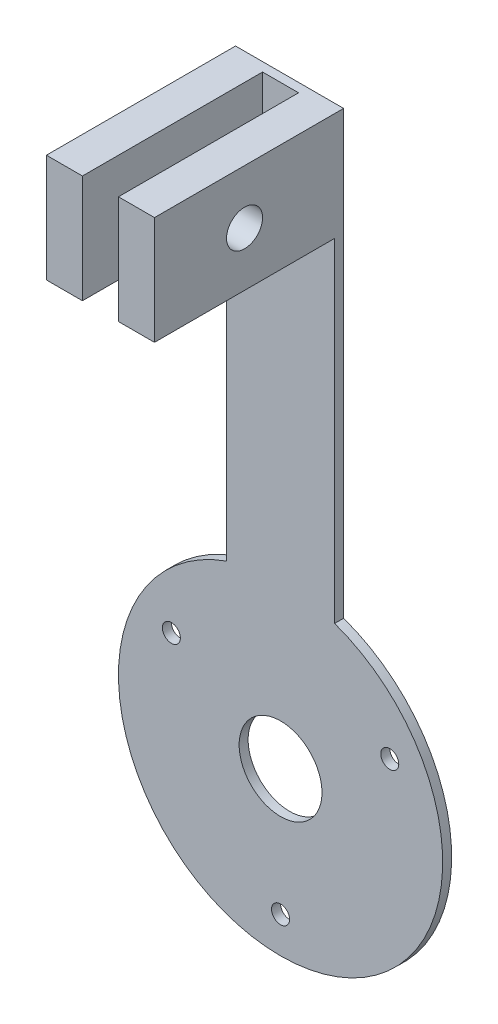
SolidWorks part; units mm, degrees
ref_plane "Front Plane" through (0, 0, 0) normal (0, 0, 1) x (1, 0, 0)
ref_plane "Top Plane" through (0, 0, 0) normal (0, 1, 0) x (1, 0, 0)
ref_plane "Right Plane" through (0, 0, 0) normal (1, 0, 0) x (0, 0, -1)
sketch "Sketch1" plane through (0, 0, 0) normal (0, 0, 1) x (1, 0, 0)
  line L1 (-88.9, 88.9) -> (88.9, 88.9)
  line L2 (-88.9, 88.9) -> (-88.9, -88.9)
  line L3 (-88.9, -88.9) -> (88.9, -88.9)
  line L4 (88.9, 88.9) -> (88.9, -88.9)
  line L5 (-88.9, 88.9) -> (88.9, -88.9) construction
  line L6 (-88.9, -88.9) -> (88.9, 88.9) construction
  line L7 (-19.05, 88.9) -> (19.05, 88.9)
  line L8 (-19.05, 88.9) -> (-19.05, 209.55)
  line L9 (-19.05, 209.55) -> (19.05, 209.55)
  line L10 (19.05, 88.9) -> (19.05, 209.55)
  circle A0 centre (0, 0) radius 14.605
  point P0 (0, 0)
  point P12 (0, 0)
  point P13 (0, 0)
  point P14 (0, 88.9)
  dimension "D2" = 29.21
  dimension "D1" = 177.8
  dimension "D3" = 38.1
  dimension "D4" = 120.65
extrude "Boss-Extrude1" add sketch "Sketch1" along normal blind 3.175 contours L1 L10 L9 L8 | L4 L1 L2 L3 A0 region at (-53.975, 86.3855, 0) region at (0, 149.225, 0)
sketch "Sketch2" plane through (0, 0, 3.175) normal (0, 0, 1) x (1, 0, 0)
  line L0 (-19.05, 209.55) -> (19.05, 209.55) construction
  line L1 (1.8142, 0) -> (50001.8142, 0) construction
  line L2 (0, 88.9) -> (0, 0) construction
  line L3 (0, 88.9) -> (-76.9897, -44.45) construction
  line L4 (-76.9897, -44.45) -> (76.9897, -44.45) construction
  line L5 (76.9897, -44.45) -> (0, 88.9) construction
  line L6 (-76.9897, -44.45) -> (0, 0) construction
  line L7 (0, 0) -> (76.9897, 44.45) construction
  line L8 (76.9897, -44.45) -> (0, 0) construction
  line L9 (0, 0) -> (-76.9897, 44.45) construction
  line L10 (0, 0) -> (0, -88.9) construction
  line L19 (88.9, -88.9) -> (88.9, 88.9)
  line L20 (88.9, 88.9) -> (-88.9, 88.9)
  line L21 (-88.9, 88.9) -> (-88.9, -88.9)
  line L22 (-88.9, -88.9) -> (88.9, -88.9)
  line L27 (-6.35, 209.55) -> (6.35, 209.55) construction
  line L28 (-19.05, 209.55) -> (-6.35, 209.55)
  line L29 (-19.05, 209.55) -> (-19.05, 171.45)
  line L30 (-19.05, 171.45) -> (-6.35, 171.45)
  line L31 (-6.35, 209.55) -> (-6.35, 171.45)
  line L32 (6.35, 209.55) -> (19.05, 209.55)
  line L33 (6.35, 209.55) -> (6.35, 171.45)
  line L34 (6.35, 171.45) -> (19.05, 171.45)
  line L35 (19.05, 209.55) -> (19.05, 171.45)
  circle A0 centre (0, 0) radius 88.9
  circle A1 centre (-38.4948, 22.225) radius 3.175
  circle A2 centre (0, -44.45) radius 3.175
  circle A3 centre (38.4948, 22.225) radius 3.175
  point P4 (0, 0)
  point P5 (-128.8861, -109.911)
  point P21 (-69.85, 88.9)
  point P23 (-69.85, -88.9)
  point P25 (69.85, -88.9)
  point P26 (69.85, 88.9)
  point P27 (-57.15, 88.9)
  point P28 (-57.15, -88.9)
  point P29 (57.15, -88.9)
  point P30 (57.15, 88.9)
  point P39 (0, 0)
  point P40 (0, 0)
  point P41 (12.8511, 77.6746)
  point P42 (31.75, 46.9484)
  point P43 (0, 209.55)
  point P44 (0, 0)
  point P45 (19.05, 77.9274)
  point P46 (31.75, 88.9)
  point P47 (19.05, 144.58)
  point P48 (6.35, 215.9)
  point P51 (38.4948, 22.225)
  dimension "D1" = 6.35
  dimension "D2" = 177.8
  dimension "D5" = 38.1
  dimension "D3" = 12.7
  dimension "D4" = 12.7
  dimension "D6" = 38.1
extrude "Cut-Extrude1" cut sketch "Sketch2" against normal through all contours A1 | A3 | A2 region at (-38.4948, 22.225, 3.175) region at (0, -44.45, 3.175) region at (38.4948, 22.225, 3.175)
extrude "Boss-Extrude2" add sketch "Sketch2<3>" along normal blind 63.5 contours L29 L31 | L35 L32 L33 L34 region at (-12.7, 190.5, 3.175) region at (12.7, 190.5, 3.175)
sketch "Sketch2<3>" plane through (0, 0, 3.175) normal (0, 0, 1) x (1, 0, 0) same geometry as "Sketch2"
sketch "Sketch3" plane through (-19.05, 0, 0) normal (-1, 0, 0) x (0, 0, 1)
  line L0 (66.675, 190.5) -> (34.925, 190.5) construction
  line L4 (66.675, 209.55) -> (66.675, 171.45) construction
  circle A2 centre (34.925, 190.5) radius 6.35
  point P2 (0, 0)
  dimension "D1" = 12.7
  dimension "D2" = 31.75
extrude "Cut-Extrude2" cut sketch "Sketch3" against normal through all contours A2 | A2 region at (-19.05, 190.5, 34.925)
sketch "Sketch4" plane through (0, 0, 3.175) normal (0, 0, 1) x (1, 0, 0)
  line L0 (0, 0) -> (49.4934, 28.575) construction
  line L1 (-19.05, 88.9) -> (-19.05, 53.8815)
  line L2 (19.05, 88.9) -> (19.05, 53.8815)
  line L12 (19.05, 171.45) -> (6.35, 171.45)
  line L13 (6.35, 171.45) -> (6.35, 209.55)
  line L14 (6.35, 209.55) -> (-6.35, 209.55)
  line L15 (-6.35, 209.55) -> (-6.35, 171.45)
  line L16 (-6.35, 171.45) -> (-19.05, 171.45)
  line L17 (-19.05, 171.45) -> (-19.05, 88.9)
  line L18 (-19.05, 88.9) -> (-88.9, 88.9)
  line L19 (-88.9, 88.9) -> (-88.9, -88.9)
  line L20 (-88.9, -88.9) -> (88.9, -88.9)
  line L21 (88.9, -88.9) -> (88.9, 88.9)
  line L22 (88.9, 88.9) -> (19.05, 88.9)
  line L23 (19.05, 88.9) -> (19.05, 171.45)
  line L24 (19.05, 171.45) -> (6.35, 171.45)
  line L25 (6.35, 171.45) -> (6.35, 209.55)
  line L26 (6.35, 209.55) -> (-6.35, 209.55)
  line L27 (-6.35, 209.55) -> (-6.35, 171.45)
  line L28 (-6.35, 171.45) -> (-19.05, 171.45)
  line L29 (-19.05, 171.45) -> (-19.05, 88.9)
  line L30 (-19.05, 88.9) -> (-88.9, 88.9)
  line L31 (-88.9, 88.9) -> (-88.9, -88.9)
  line L32 (-88.9, -88.9) -> (88.9, -88.9)
  line L33 (88.9, -88.9) -> (88.9, 88.9)
  line L34 (88.9, 88.9) -> (19.05, 88.9)
  line L35 (19.05, 88.9) -> (19.05, 171.45)
  circle A0 centre (0, 0) radius 57.15
  point P6 (38.4948, 22.225)
  point P10 (49.4934, 28.575)
  point P12 (27.2419, 28.1124)
  line M26 (-19.05, 88.9) -> (-88.9, 88.9)
  line M27 (-88.9, 88.9) -> (-88.9, -88.9)
  line M28 (-88.9, -88.9) -> (88.9, -88.9)
  line M29 (88.9, -88.9) -> (88.9, 88.9)
  line M30 (88.9, 88.9) -> (19.05, 88.9)
  dimension "D2" = 12.7
  dimension "D1" = 0
extrude "Cut-Extrude3" cut sketch "Sketch4" against normal through all contours A0 L1 L2 M26 M27 M28 M29 M30 region at (-21.5645, 71.3908, 3.175)
